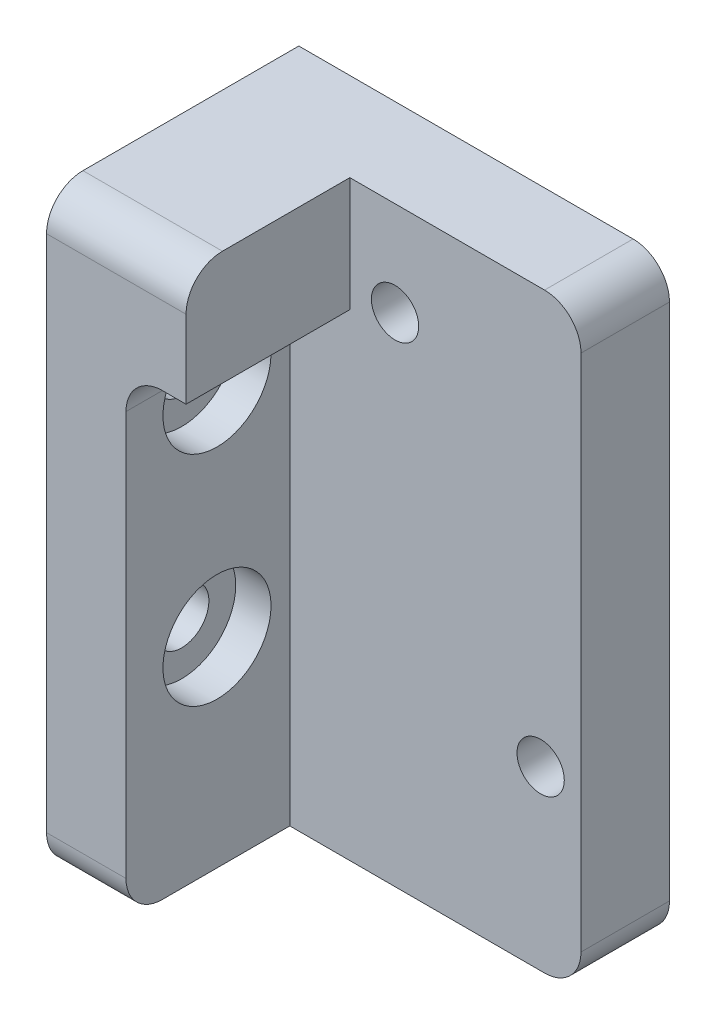
SolidWorks part; units mm, degrees
ref_plane "Front Plane" through (0, 0, 0) normal (0, 0, 1) x (1, 0, 0)
ref_plane "Top Plane" through (0, 0, 0) normal (0, 1, 0) x (1, 0, 0)
ref_plane "Right Plane" through (0, 0, 0) normal (1, 0, 0) x (0, 0, -1)
sketch "Sketch1" plane through (0, 0, 0) normal (0, 0, 1) x (1, 0, 0)
  line L1 (0, 0) -> (20.32, 0)
  line L2 (0, 0) -> (0, 31.75)
  line L3 (0, 31.75) -> (20.32, 31.75)
  line L4 (20.32, 0) -> (20.32, 31.75)
  dimension "D1" = 20.32
  dimension "D2" = 31.75
extrude "Boss-Extrude1" add sketch "Sketch1" along normal blind 3
sketch "Sketch2" plane through (0, 0, 0) normal (0, 1, 0) x (1, 0, 0)
  line L10 (0, -3) -> (20.32, -3) construction
  line L11 (0, 0) -> (-2.3695, 0)
  line L12 (0, 0) -> (0, -14.43)
  line L13 (0, -14.43) -> (-2.3695, -14.43)
  line L14 (-2.3695, 0) -> (-2.3695, -14.43)
  point P5 (-1.1847, -14.43)
  dimension "D1" = 11.43
extrude "Boss-Extrude2" add sketch "Sketch2" along normal up to surface (31.75 mm away) up to face at (10.16, 31.75, 1.5)
sketch "Sketch5" plane through (0, 0, 3) normal (0, 0, 1) x (1, 0, 0)
  line L0 (7.3451, 28.3425) -> (17.5051, 5.9905) construction
  line L6 (20.4261, 31.708) -> (19.996, 30.9262) construction
  circle A0 centre (7.3451, 28.3425) radius 1.65
  circle A1 centre (17.5051, 5.9905) radius 1.65
  point P12 (7.3451, 28.3425)
  dimension "D1" = 3.3
  dimension "D2" = 3.3
  dimension "D3" = 22.352
  dimension "D4" = 10.16
extrude "Cut-Extrude2" cut sketch "Sketch5" against normal blind 3
sketch "Sketch6" plane through (0, 0, 3) normal (0, 0, 1) x (1, 0, 0)
  line L1 (0, 31.75) -> (4.318, 31.75)
  line L2 (0, 31.75) -> (0, 20.32)
  line L3 (0, 20.32) -> (4.318, 20.32)
  line L4 (4.318, 31.75) -> (4.318, 20.32)
  dimension "D1" = 4.318
  dimension "D2" = 11.43
sketch "Sketch7" plane through (0, 0, 0) normal (0, 0, 1) x (1, 0, 0)
  line L0 (7.3451, 28.3425) -> (17.5051, 5.9905) construction
  line L1 (18.3941, 2.625) -> (6.4561, 2.625)
  line L2 (20.4261, 4.657) -> (20.4261, 29.676)
  line L3 (18.3941, 31.708) -> (6.4561, 31.708)
  line L4 (4.4241, 4.657) -> (4.4241, 29.676)
  line L5 (20.4261, 2.625) -> (4.4241, 31.708) construction
  line L6 (20.4261, 31.708) -> (4.4241, 2.625) construction
  circle A0 centre (7.3451, 28.3425) radius 1.65
  circle A1 centre (17.5051, 5.9905) radius 1.65
  arc A2 (20.4261, 29.676) -> (18.3941, 31.708) centre (18.3941, 29.676) ccw
  arc A3 (18.3941, 2.625) -> (20.4261, 4.657) centre (18.3941, 4.657) ccw
  arc A4 (6.4561, 2.625) -> (4.4241, 4.657) centre (6.4561, 4.657) cw
  arc A5 (6.4561, 31.708) -> (4.4241, 29.676) centre (6.4561, 29.676) ccw
  point P4 (12.4251, 17.1665)
  point P9 (12.4251, 17.1665)
  point P12 (7.3451, 28.3425)
  dimension "D1" = 3.3
  dimension "D2" = 3.3
  dimension "D3" = 22.352
  dimension "D4" = 10.16
  dimension "D8" = 2.032
  dimension "D5" = 16.002
  dimension "D6" = 29.083
  dimension "D7" = 0
sketch "Sketch9" plane through (0, 0, 0) normal (0, 1, 0) x (1, 0, 0)
  line L0 (0, -14.43) -> (0, -3) construction
  line L1 (-2.3695, 0) -> (0, 0)
  line L2 (-2.3695, 0) -> (-2.3695, 3.175)
  line L3 (-2.3695, 3.175) -> (0, 3.175)
  line L4 (0, 0) -> (0, 3.175)
  dimension "D1" = 3.175
extrude "Boss-Extrude4" add sketch "Sketch9" along normal up to surface (31.75 mm away) up to face at (5.9835, 31.75, 5.81)
extrude "Boss-Extrude5" [suppressed] add sketch "Sketch6" along normal blind 8.334
sketch "Sketch10" plane through (-2.3695, 0, 0) normal (-1, 0, 0) x (0, 0, 1)
  line L0 (14.43, 31.75) -> (14.43, 0) construction
  line L1 (-3.175, 31.75) -> (14.43, 31.75)
  line L2 (-3.175, 31.75) -> (-3.175, 0)
  line L3 (-3.175, 0) -> (14.43, 0)
  line L4 (14.43, 31.75) -> (14.43, 0)
extrude "Boss-Extrude6" add sketch "Sketch10" along normal blind 3.175
hole_wizard "CBORE for #6 Pan Head Machine Screw1" positions "Sketch11" profile "Sketch12" counterbore size "#6" standard "ANSI Inch" end condition through all
sketch "Sketch11" plane through (0, 0, 0) normal (1, 0, 0) x (0, 0, -1)
  line L0 (-14.43, 31.75) -> (-14.43, 0) construction
  line L1 (-3, 31.75) -> (-14.43, 31.75) construction
  line L2 (-14.43, 0) -> (-3, 0) construction
  point P0 (-8.08, 22.86)
  point P2 (-8.08, 7.62)
  dimension "D1" = 6.35
  dimension "D2" = 6.35
  dimension "D3" = 8.89
  dimension "D4" = 7.62
sketch "Sketch12" plane through (0, 22.86, 8.08) normal (0, 1, 0) x (0, 0, -1)
  line L0 (0, 0) -> (0, 5.5445)
  line L1 (0, 5.5445) -> (1.8986, 5.5445)
  line L3 (1.8986, 5.5445) -> (1.8986, 2.4638)
  line L4 (1.8986, 2.4638) -> (3.7706, 2.4638)
  line L5 (3.7706, 2.4638) -> (3.7706, 0)
  line L7 (3.7706, 0) -> (0, 0)
  line L11 (0, -6.35) -> (0, 107.95) construction
  dimension "Thru Hole Dia." = 3.7973
  dimension "Thru Hole Depth" = 5.5445
  dimension "C'Bore Dia." = 7.5413
  dimension "C'Bore Depth" = 2.4638
sketch "Sketch14" plane through (0, 31.75, 0) normal (0, 1, 0) x (1, 0, 0)
  line L0 (-5.5445, -14.43) -> (-5.5445, 3.175) construction
  line L1 (20.32, -3) -> (-5.5445, -3)
  line L2 (20.32, -3) -> (20.32, 0)
  line L3 (20.32, 0) -> (-5.5445, 0)
  line L4 (-5.5445, -3) -> (-5.5445, 0)
extrude "Boss-Extrude7" add sketch "Sketch14" along normal blind 3.175
sketch "Sketch15" plane through (0, 31.75, 0) normal (0, 1, 0) x (1, 0, 0)
  line L1 (0, 0) -> (-5.5445, 0)
  line L2 (0, 0) -> (0, 3.175)
  line L3 (0, 3.175) -> (-5.5445, 3.175)
  line L4 (-5.5445, 0) -> (-5.5445, 3.175)
extrude "Boss-Extrude8" add sketch "Sketch15" along normal blind 3.175
sketch "Sketch17" plane through (0, 31.75, 0) normal (0, 1, 0) x (1, 0, 0)
  line L1 (0, -3) -> (-5.5445, -3)
  line L2 (0, -3) -> (0, -14.43)
  line L3 (0, -14.43) -> (-5.5445, -14.43)
  line L4 (-5.5445, -3) -> (-5.5445, -14.43)
extrude "Boss-Extrude9" add sketch "Sketch17" along normal blind 3.175
sketch "Sketch18" plane through (0, 0, 0) normal (1, 0, 0) x (0, 0, -1)
  line L0 (-14.43, 34.925) -> (-14.43, 0) construction
  line L1 (-3, 34.925) -> (-14.43, 34.925)
  line L2 (-3, 34.925) -> (-3, 26.9468)
  line L3 (-3, 26.9468) -> (-14.43, 26.9468)
  line L4 (-14.43, 34.925) -> (-14.43, 26.9468)
extrude "Boss-Extrude10" add sketch "Sketch18" along normal blind 4.191
sketch "Sketch19" plane through (0, 0, 0) normal (0, 0, -1) x (-1, 0, 0)
  line L1 (0, 34.925) -> (-20.32, 34.925)
  line L2 (0, 34.925) -> (0, 0)
  line L3 (0, 0) -> (-20.32, 0)
  line L4 (-20.32, 34.925) -> (-20.32, 0)
  circle A0 centre (-7.3451, 28.3425) radius 1.6027
  circle A1 centre (-17.5051, 5.9905) radius 1.65
extrude "Boss-Extrude11" add sketch "Sketch19" along normal up to surface (3.175 mm away) up to face at (-2.7722, 17.4625, -3.175)
fillet "Fillet6" radius 2.54 1 edges at (0, 26.9468, 8.715)
fillet "Fillet5" radius 2.54 2 edges at (-0.6767, 34.925, 14.43) (20.32, 34.925, -0.0875)
sketch "Sketch20" plane through (0, 0, 0) normal (0, -1, 0) x (-1, 0, 0)
  line L1 (0, -14.43) -> (5.5445, -14.43)
  line L2 (0, -14.43) -> (0, -3)
  line L3 (0, 3.175) -> (5.5445, 3.175)
  line L4 (5.5445, -14.43) -> (5.5445, 3.175)
  line L5 (-20.32, -3) -> (0, -3)
  line L6 (-20.32, -3) -> (-20.32, 3.175)
  line L7 (-20.32, 3.175) -> (0, 3.175)
extrude "Boss-Extrude12" add sketch "Sketch20" along normal blind 6.35
fillet "Fillet7" radius 2.54 2 edges at (20.32, -6.35, -0.0875) (-2.7722, -6.35, 14.43)
